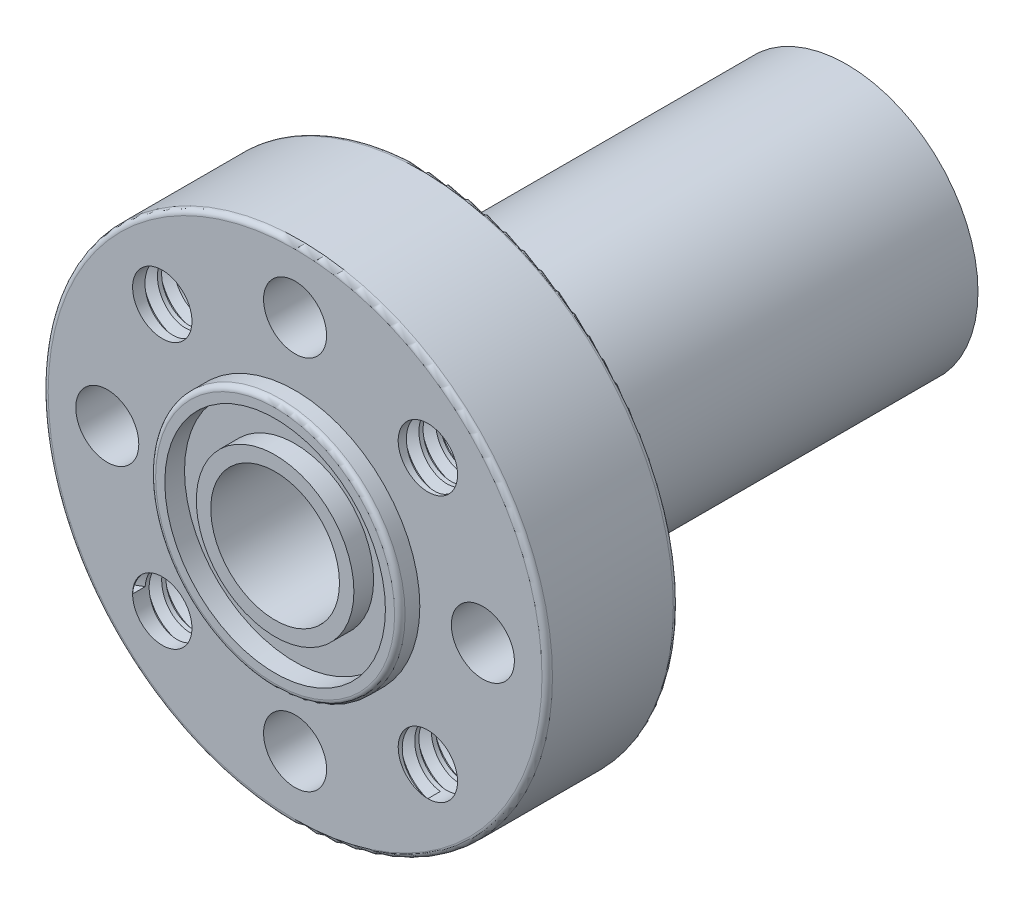
SolidWorks part; units mm, degrees
ref_plane "Front Plane" through (0, 0, 0) normal (0, 0, 1) x (1, 0, 0)
ref_plane "Top Plane" through (0, 0, 0) normal (0, 1, 0) x (1, 0, 0)
ref_plane "Right Plane" through (0, 0, 0) normal (1, 0, 0) x (0, 0, -1)
sketch "Sketch1" plane through (0, 0, 0) normal (0, 0, 1) x (1, 0, 0)
  circle A0 centre (0, 0) radius 9.6
  dimension "D1" = 19.2
extrude "Boss-Extrude1" add sketch "Sketch1" along normal blind 5 contours A0
sketch "Sketch4" plane through (0, 0, 5) normal (0, 0, 1) x (1, 0, 0)
  circle A0 centre (0, 0) radius 4.75
  dimension "D1" = 9.5
extrude "Boss-Extrude4" add sketch "Sketch4" along normal blind 0.76 contours A0
sketch "Sketch5" plane through (0, 0, 5.76) normal (0, 0, 1) x (1, 0, 0)
  circle A0 centre (0, 0) radius 2.45
  dimension "D1" = 4.9
extrude "Cut-Extrude2" cut sketch "Sketch5" against normal through all
sketch "Sketch6" plane through (0, 0, 5.76) normal (0, 0, 1) x (1, 0, 0)
  circle A0 centre (0, 0) radius 3
  circle A1 centre (0, 0) radius 4.2
  dimension "D1" = 8.4
  dimension "D2" = 6
extrude "Cut-Extrude3" cut sketch "Sketch6" against normal blind 0.75
fillet "Fillet1" radius 0.2 3 edges at (4.75, 0, 5.76) (9.6, 0, 0) (9.6, 0, 5)
sketch "Sketch7" plane through (0, 0, 5) normal (0, 0, 1) x (1, 0, 0)
  circle A0 centre (0, -7.15) radius 1.2
  dimension "D1" = 2.4
extrude "Cut-Extrude5" cut sketch "Sketch7" against normal through all contours A0
sketch "Sketch9" plane through (0, 0, 5) normal (0, 0, 1) x (1, 0, 0)
  arc A1 (0, -7.15) -> (-5.0558, -5.0558) centre (0, 0) cw construction
  circle A2 centre (-5.0558, -5.0558) radius 1.13
  dimension "D1" = 45
  dimension "D2" = 2.26
extrude "Cut-Extrude4" cut sketch "Sketch9" against normal through all contours A2
thread "Thread1" pitch 0.635 method cut profile "Thread Profile2" start angle 0, offset 0, length 0, pitch 0.635, diameter 2.26
ref_plane "Plane2" through (-6.1858, -5.0558, 5) normal (0, -1, 0) x (-1, 0, 0)
sketch "Thread Profile2" plane through (-6.1858, -5.0558, 5) normal (0, -1, 0) x (-1, 0, 0)
  line L0 (0, 0) -> (0, 0.635) construction
  line L1 (0, 0) -> (0.3437, 0.1984)
  line L2 (0.3437, 0.1984) -> (0.3437, 0.2778)
  line L3 (0.3437, 0.2778) -> (0, 0.4762)
  line L4 (0.3437, 0.2381) -> (0, 0.2381) construction
  line L11 (0, 0) -> (0, 0.4762)
  point P2 (0, 0)
  dimension "Pitch" = 0.635
  dimension "Profile_Angle" = 60
  dimension "Profile_Land" = 0.0794
  dimension "Profile_Height" = 0.3437
sketch "Sketch20" plane through (0, 0, 0) normal (0, 1, 0) x (1, 0, 0)
  line L0 (0, -6.3944) -> (0, 0.7339) construction
pattern_circular "CirPattern1" count 4 every 90 about axis through (0, 0, 6.3944) along (0, 0, -1) of "Cut-Extrude4", "Thread1", "Cut-Extrude5"
sketch "Sketch21" plane through (0, 0, 0) normal (0, 0, -1) x (-1, 0, 0)
  circle A0 centre (0, 0) radius 4
  circle A1 centre (0, 0) radius 5
extrude "Boss-Extrude5" add sketch "Sketch21" along normal blind 16 contours A0 | A1
